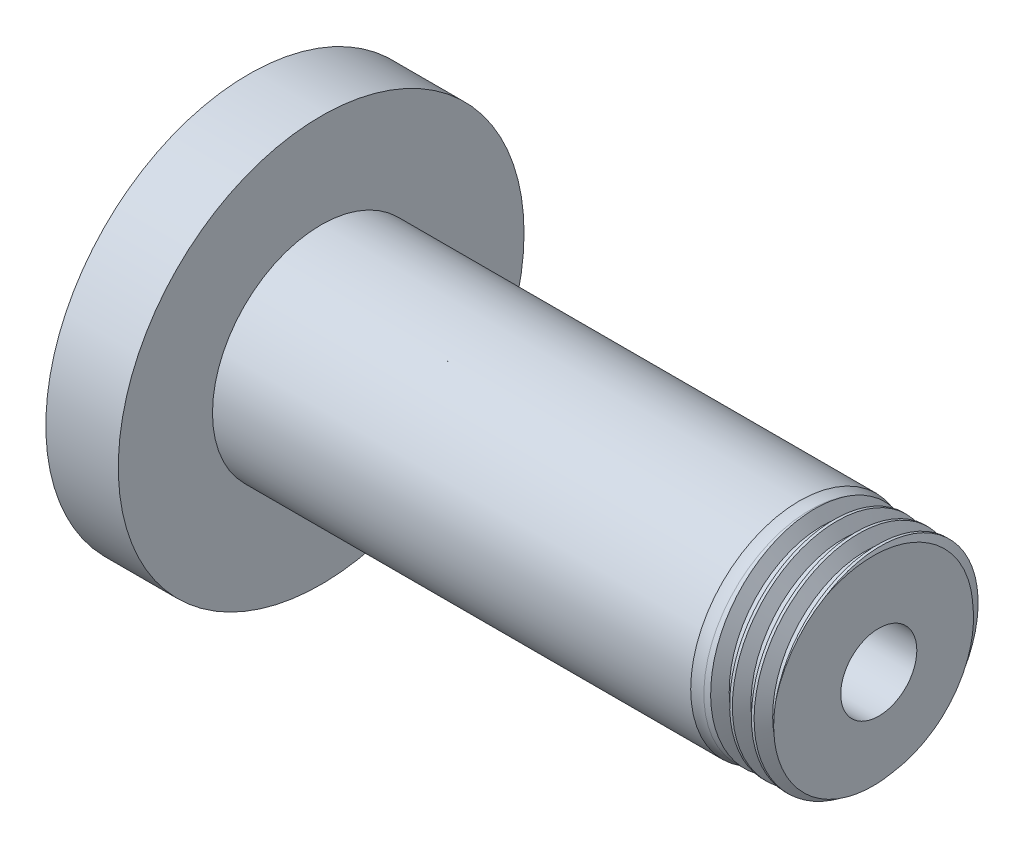
SolidWorks part; units mm, degrees
material "PLA Density Only"
ref_plane "Front Plane" through (0, 0, 0) normal (0, 0, 1) x (1, 0, 0)
ref_plane "Top Plane" through (0, 0, 0) normal (0, 1, 0) x (1, 0, 0)
ref_plane "Right Plane" through (0, 0, 0) normal (1, 0, 0) x (0, 0, -1)
sketch "Sketch1" plane through (0, 0, 0) normal (1, 0, 0) x (0, 0, -1)
  circle A0 centre (0, 0) radius 14
  dimension "D1" = 28
extrude "Boss-Extrude1" add sketch "Sketch1" along normal blind 5
sketch "Sketch2" plane through (5, 0, 0) normal (1, 0, 0) x (0, 0, -1)
  circle A0 centre (0, 0) radius 7.35
  dimension "D1" = 14.7
extrude "Boss-Extrude2" add sketch "Sketch2" along normal blind 38.48
thread "Thread1" pitch 1.5 method cut profile "Thread Profile1" start angle 0, offset 33.48, length 5, pitch 1.5, diameter 14.7
ref_plane "Plane1" through (38.48, 0, -7.35) normal (0, -1, 0) x (0, 0, -1)
sketch "Thread Profile1" plane through (38.48, 0, -7.35) normal (0, -1, 0) x (0, 0, -1)
  line L0 (0, 0) -> (0, 1.5) construction
  line L11 (0, 0) -> (0, 1.3125)
  line L12 (0, 1.3125) -> (-0.8119, 0.8437)
  line L13 (-0.8119, 0.8437) -> (-0.8119, 0.4687)
  line L15 (-0.8119, 0.4687) -> (0, 0)
  line L17 (-0.8119, 0.6562) -> (0, 0.6562) construction
  point P2 (0, 0)
  dimension "Pitch" = 1.5
  dimension "Profile_Angle" = 60
  dimension "Profile_Land" = 0.375
  dimension "Profile_Height" = 0.8119
sketch "Sketch5" plane through (0, 0, 0) normal (0, 1, 0) x (1, 0, 0)
  line L4 (38.48, 7.35) -> (38.9487, 6.5381)
  line L5 (38.9487, 6.5381) -> (39.3237, 6.5381)
  line L6 (39.3237, 6.5381) -> (39.7925, 7.35)
  line L7 (39.7925, 7.35) -> (38.48, 7.35)
  line L8 (38.48, 7.35) -> (38.9487, 6.5381)
  line L9 (38.9487, 6.5381) -> (39.3237, 6.5381)
  line L10 (39.3237, 6.5381) -> (39.7925, 7.35)
  line L11 (39.7925, 7.35) -> (38.48, 7.35)
  dimension "D1" = 0
extrude "Cut-Extrude1" cut sketch "Sketch5" against normal through all
sketch "Sketch6" plane through (0, 0, 0) normal (-1, 0, 0) x (0, 0, 1)
  circle A0 centre (0, 0) radius 2.625
  dimension "D1" = 5.25
extrude "Cut-Extrude2" cut sketch "Sketch6" against normal through all
sketch "Sketch7" plane through (5, 0, 0) normal (1, 0, 0) x (0, 0, -1)
  circle A0 centre (0, 0) radius 7.5
  circle A1 centre (0, 0) radius 2.625
  dimension "D1" = 15
  dimension "D2" = 5.25
extrude "Boss-Extrude3" add sketch "Sketch7" along normal blind 33
fillet "Fillet1" radius 2 1 edges at (38, 0, -7.35)
